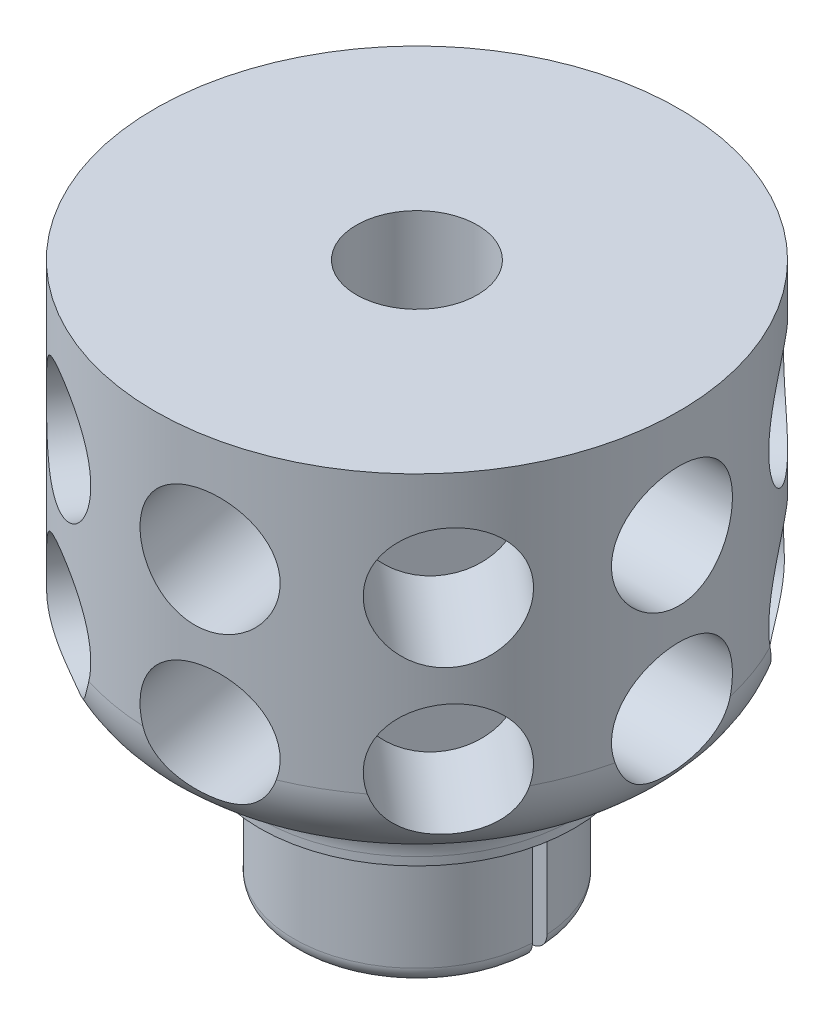
SolidWorks part; units mm, degrees
ref_plane "Front Plane" through (0, 0, 0) normal (0, 0, 1) x (1, 0, 0)
ref_plane "Top Plane" through (0, 0, 0) normal (0, 1, 0) x (1, 0, 0)
ref_plane "Right Plane" through (0, 0, 0) normal (1, 0, 0) x (0, 0, -1)
sketch "Sketch1" plane through (0, 0, 0) normal (0, 1, 0) x (1, 0, 0)
  circle A0 centre (0, 0) radius 32.5
  dimension "D1" = 65
extrude "Boss-Extrude1" add sketch "Sketch1" along normal blind 44.3
sketch "Sketch3" plane through (0, 0, 0) normal (0, -1, 0) x (1, 0, 0)
  circle A0 centre (0, 0) radius 19.5
  dimension "D1" = 39
extrude "Boss-Extrude2" add sketch "Sketch3" along normal blind 7
sketch "Sketch4" plane through (0, -7, 0) normal (0, -1, 0) x (1, 0, 0)
  circle A0 centre (0, 0) radius 15.25
  dimension "D1" = 30.5
extrude "Boss-Extrude3" add sketch "Sketch4" along normal blind 16
fillet "Fillet1" radius 6 1 edges at (0, 0, -19.5)
sketch "Sketch7" plane through (0, -23, 0) normal (0, -1, 0) x (1, 0, 0)
  line L1 (33.0968, 0.9034) -> (-33.0968, 0.9034)
  line L2 (33.0968, 0.9034) -> (33.0968, -0.9034)
  line L3 (33.0968, -0.9034) -> (-33.0968, -0.9034)
  line L4 (-33.0968, 0.9034) -> (-33.0968, -0.9034)
  line L5 (33.0968, 0.9034) -> (-33.0968, -0.9034) construction
  line L6 (33.0968, -0.9034) -> (-33.0968, 0.9034) construction
  point P0 (0, 0)
extrude "Cut-Extrude2" cut sketch "Sketch7" against normal up to surface (16 mm away) up to face at (0, -7, -15.25)
fillet "Fillet2" radius 2 2 edges at (0, -23, 15.25) (0, -23, -15.25)
sketch "Sketch11" plane through (0, 44.3, 0) normal (0, 1, 0) x (1, 0, 0)
  line L0 (0, 0) -> (0, -50000) construction
  line L6 (3.4, 32.3217) -> (-3.4, 32.3217)
  line L7 (3.4, 32.3217) -> (3.4, 23.3217)
  line L8 (3.4, 23.3217) -> (-3.4, 23.3217)
  line L9 (-3.4, 32.3217) -> (-3.4, 23.3217)
  circle A2 centre (0, 0) radius 32.5 construction
  dimension "D1" = 6.8
  dimension "D2" = 9
extrude "Boss-Extrude4" add sketch "Sketch11" against normal up to next (44.3 mm away)
ref_plane "Plane1" through (32.5, 0, 0) normal (1, 0, 0) x (0, 0, -1)
sketch "Sketch14" plane through (32.5, 0, 0) normal (1, 0, 0) x (0, 0, -1)
  line L0 (-32.5, 0) -> (32.5, 0) construction
  circle A0 centre (0, 12) radius 7.5
  circle A1 centre (0, 30.9111) radius 7.5
  dimension "D1" = 15
  dimension "D2" = 12
extrude "Cut-Extrude6" cut sketch "Sketch14" against normal blind 14
pattern_circular "CirPattern4" count 9 over 360 about axis through (0, 44.3, 0) along (0, -1, 0) of "Cut-Extrude6" reverse direction yes
fillet "Fillet3" radius 10 1 edges at (0, 0, 32.5)
sketch "Sketch15" plane through (0, 44.3, 0) normal (0, 1, 0) x (1, 0, 0)
  circle A0 centre (0, 0) radius 7.5
  dimension "D1" = 15
extrude "Cut-Extrude7" cut sketch "Sketch15" against normal through all
